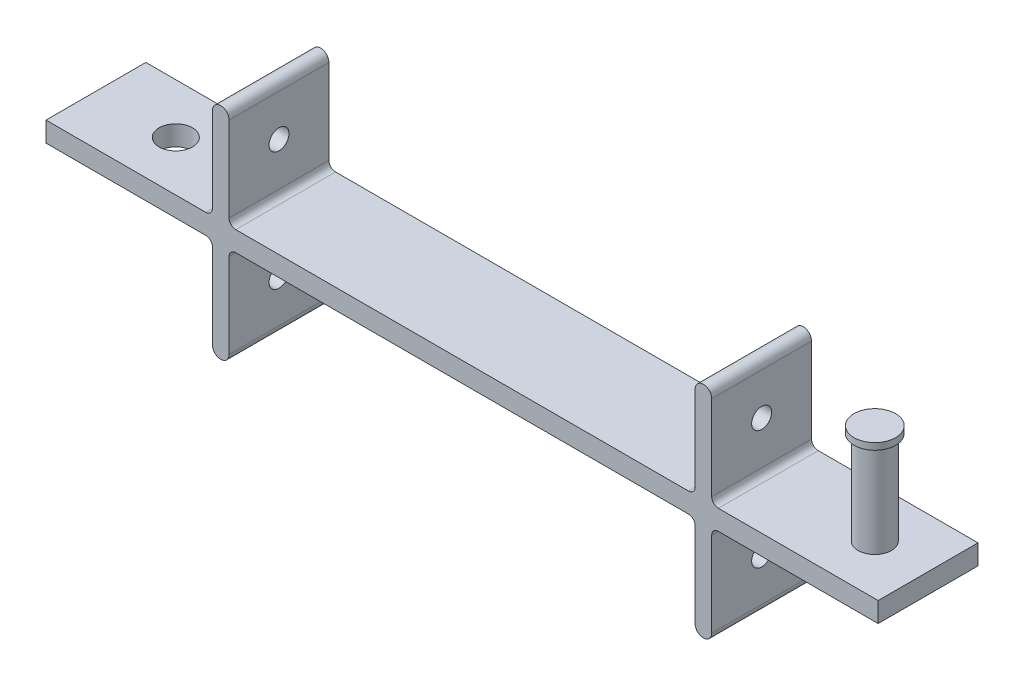
SolidWorks part; units mm, degrees
material "1100-H26 Rod (SS)"
ref_plane "Front Plane" through (0, 0, 0) normal (0, 0, 1) x (1, 0, 0)
ref_plane "Top Plane" through (0, 0, 0) normal (0, 1, 0) x (1, 0, 0)
ref_plane "Right Plane" through (0, 0, 0) normal (1, 0, 0) x (0, 0, -1)
sketch "Sketch1" plane through (0, 0, 0) normal (0, 0, 1) x (1, 0, 0)
  line L0 (-28.8636, 0) -> (-48.8636, 0)
  line L1 (-28.8636, 0) -> (-28.8636, 6)
  line L2 (-28.8636, 6) -> (-48.8636, 6)
  line L3 (-48.8636, 6) -> (-48.8636, 36)
  line L4 (-48.8636, 36) -> (-53.8636, 36)
  line L5 (-53.8636, 36) -> (-53.8636, 6)
  line L6 (-53.8636, 6) -> (-193.8636, 6)
  line L7 (-193.8636, 6) -> (-193.8636, 36)
  line L8 (-193.8636, 36) -> (-198.8636, 36)
  line L9 (-198.8636, 36) -> (-198.8636, 6)
  line L10 (-198.8636, 6) -> (-218.8636, 6)
  line L11 (-218.8636, 6) -> (-218.8636, 0)
  line L12 (-198.8636, 0) -> (-218.8636, 0)
  line L13 (-193.8636, 0) -> (-53.8636, 0)
  line L15 (-48.8636, 0) -> (-48.8636, -30)
  line L16 (-48.8636, -30) -> (-53.8636, -30)
  line L17 (-53.8636, 0) -> (-53.8636, -30)
  line L18 (-193.8636, 0) -> (-193.8636, -30)
  line L19 (-193.8636, -30) -> (-198.8636, -30)
  line L20 (-198.8636, 0) -> (-198.8636, -30)
  dimension "D1" = 140
  dimension "D2" = 150
  dimension "D3" = 30
  dimension "D4" = 20
  dimension "D5" = 6
  dimension "D6" = 5
  dimension "D7" = 30
  dimension "D8" = 30
  dimension "D9" = 5
extrude "Boss-Extrude1" add sketch "Sketch1" along normal blind 30
sketch "Sketch2" plane through (-198.8636, 0, 0) normal (-1, 0, 0) x (0, 0, 1)
  line L0 (15, 6) -> (15, 21) construction
  line L1 (30, 6) -> (0, 6) construction
  circle A0 centre (15, 21) radius 3
  dimension "D2" = 6
  dimension "D1" = 15
fillet "Fillet1" radius 2 2 edges at (-193.8636, 6, 15) (-198.8636, 6, 15)
fillet "Fillet2" 2 edges at (-198.8636, 36, 15) (-193.8636, 36, 15) type full round first side face at (-198.8636, 22, 15) second side face at (-193.8636, 22, 15) middle face at (-196.3636, 36, 15)
fillet "Fillet3" 2 edges at (-53.8636, 36, 15) (-48.8636, 36, 15) type full round first side face at (-53.8636, 21, 15) second side face at (-48.8636, 21, 15) middle face at (-51.3636, 36, 15)
fillet "Fillet4" radius 2 2 edges at (-48.8636, 6, 15) (-53.8636, 6, 15)
extrude "Cut-Extrude4" cut sketch "Sketch2" against normal blind 163 contours A0
sketch "Sketch9" plane through (0, 0, 0) normal (0, 0, -1) x (-1, 0, 0)
  line L1 (218.8636, 6) -> (228.8636, 6)
  line L2 (218.8636, 6) -> (218.8636, 0)
  line L3 (218.8636, 0) -> (228.8636, 0)
  line L4 (228.8636, 6) -> (228.8636, 0)
  dimension "D1" = 10
extrude "Boss-Extrude8" add sketch "Sketch9" against normal blind 30
sketch "Sketch14" plane through (0, 0, 0) normal (0, 0, -1) x (-1, 0, 0)
  line L1 (228.8636, 6) -> (248.8636, 6)
  line L2 (228.8636, 6) -> (228.8636, 0)
  line L3 (228.8636, 0) -> (248.8636, 0)
  line L4 (248.8636, 6) -> (248.8636, 0)
  dimension "D1" = 20
extrude "Boss-Extrude12" add sketch "Sketch14" against normal blind 30
fillet "Fillet10" 2 edges at (-48.8636, -30, 15) (-53.8636, -30, 15) type full round first side face at (-48.8636, -15, 15) second side face at (-53.8636, -15, 15) middle face at (-51.3636, -30, 15)
fillet "Fillet11" 2 edges at (-193.8636, -30, 15) (-198.8636, -30, 15) type full round first side face at (-193.8636, -15, 15) second side face at (-198.8636, -15, 15) middle face at (-196.3636, -30, 15)
fillet "Fillet12" radius 2 4 edges at (-198.8636, 0, 15) (-193.8636, 0, 15) (-53.8636, 0, 15) (-48.8636, 0, 15)
sketch "Sketch16" plane through (-48.8636, 0, 0) normal (1, 0, 0) x (0, 0, -1)
  line L0 (-15, -2) -> (-15, -27.5) construction
  line L1 (0, -2) -> (-30, -2) construction
  line L2 (-30, -27.5) -> (0, -27.5) construction
  circle A0 centre (-15, -14.75) radius 3
  dimension "D1" = 6
extrude "Cut-Extrude6" cut sketch "Sketch16" against normal blind 200
sketch "Sketch17" plane through (0, 0, 0) normal (0, 0, -1) x (-1, 0, 0)
  line L1 (28.8636, 6) -> (-1.1364, 6)
  line L2 (28.8636, 6) -> (28.8636, 0)
  line L3 (28.8636, 0) -> (-1.1364, 0)
  line L4 (-1.1364, 6) -> (-1.1364, 0)
  dimension "D1" = 30
extrude "Boss-Extrude15" add sketch "Sketch17" against normal blind 30
sketch "Sketch20" plane through (0, 0, 0) normal (0, -1, 0) x (-1, 0, 0)
  line L0 (46.8636, -15) -> (14.8636, -15) construction
  line L1 (46.8636, -30) -> (46.8636, 0) construction
  circle A0 centre (14.8636, -15) radius 5
  dimension "D2" = 10
  dimension "D1" = 32
extrude "Boss-Extrude16" add sketch "Sketch20" against normal blind 36
sketch "Sketch21" plane through (0, 36, 0) normal (0, 1, 0) x (-1, 0, 0)
  circle A0 centre (14.8636, 15) radius 6.25
  dimension "D1" = 12.5
extrude "Boss-Extrude17" add sketch "Sketch21" against normal blind 2
sketch "Sketch22" plane through (0, 6, 0) normal (0, 1, 0) x (1, 0, 0)
  line L0 (-200.8636, -15) -> (-248.8636, -15) construction
  line L1 (-200.8636, -30) -> (-200.8636, 0) construction
  line L2 (-248.8636, -30) -> (-248.8636, 0) construction
  circle A0 centre (-224.8636, -15) radius 5
  dimension "D1" = 10
extrude "Cut-Extrude7" cut sketch "Sketch22" against normal blind 10
